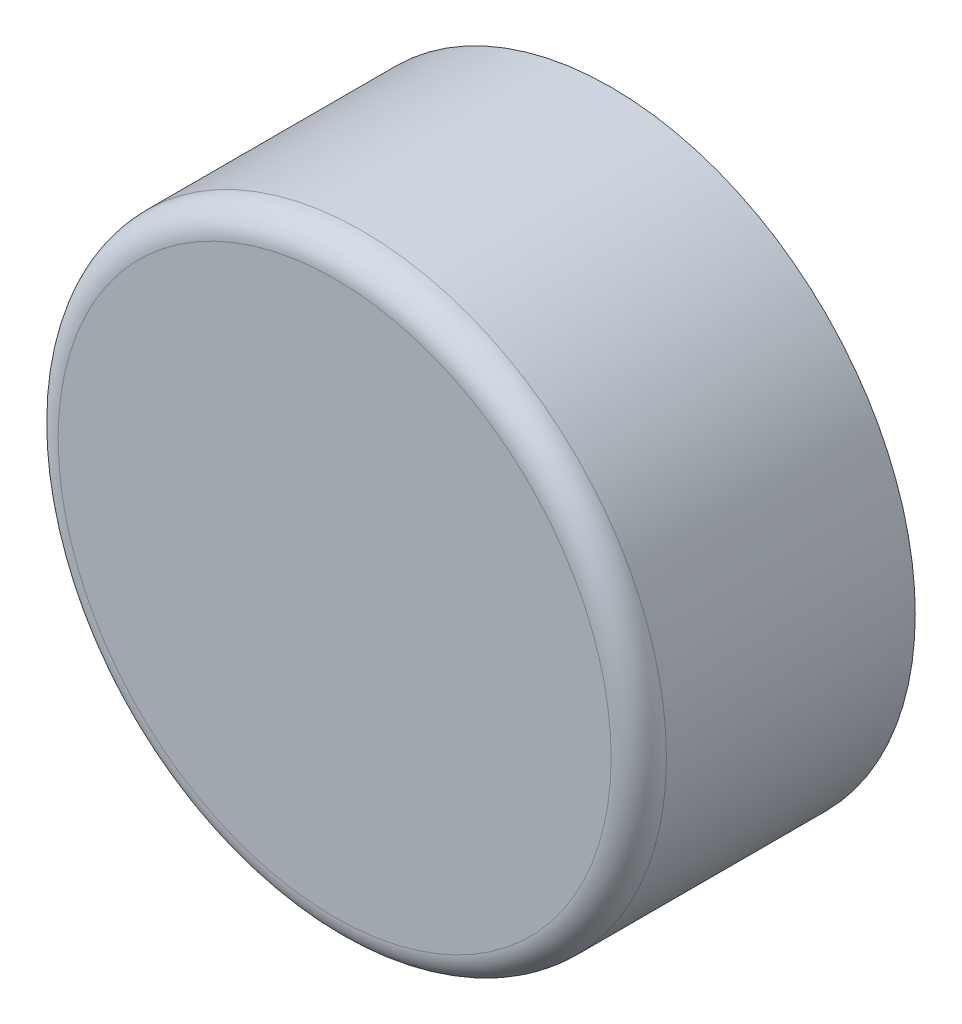
SolidWorks part; units mm, degrees
ref_plane "Front Plane" through (0, 0, 0) normal (0, 0, 1) x (1, 0, 0)
ref_plane "Top Plane" through (0, 0, 0) normal (0, 1, 0) x (1, 0, 0)
ref_plane "Right Plane" through (0, 0, 0) normal (1, 0, 0) x (0, 0, -1)
sketch "Sketch1" plane through (0, 0, 0) normal (0, 0, 1) x (1, 0, 0)
  circle A0 centre (0, 0) radius 5.5
  dimension "D1" = 11
extrude "Boss-Extrude1" add sketch "Sketch1" along normal blind 5
fillet "Fillet1" radius 0.5 1 edges at (5.5, 0, 5)
